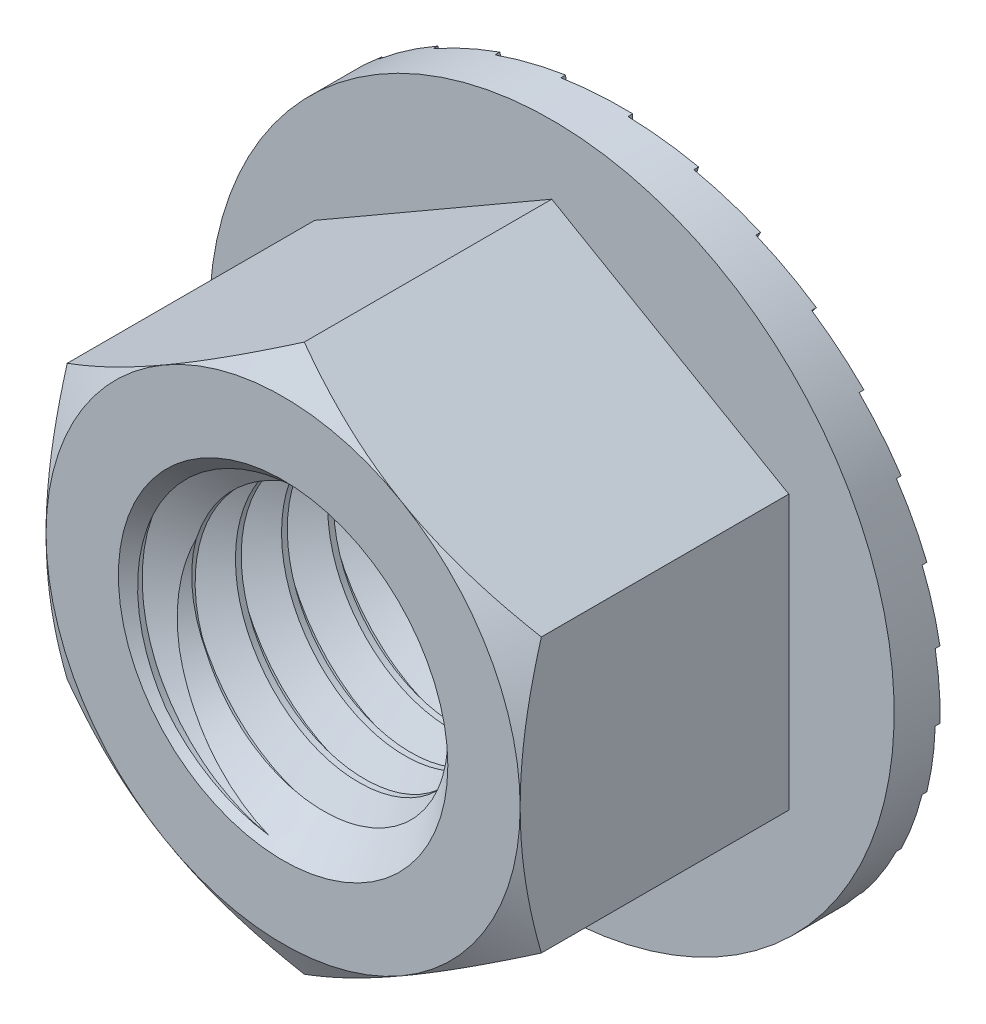
SolidWorks part; units mm, degrees
ref_plane "Front Plane" through (0, 0, 0) normal (0, 0, 1) x (1, 0, 0)
ref_plane "Top Plane" through (0, 0, 0) normal (0, 1, 0) x (1, 0, 0)
ref_plane "Right Plane" through (0, 0, 0) normal (1, 0, 0) x (0, 0, -1)
sketch "Sketch1" plane through (0, 0, 0) normal (0, 0, 1) x (1, 0, 0)
  line L1 (0, 10.3923) -> (-9, 5.1962)
  line L2 (-9, 5.1962) -> (-9, -5.1962)
  line L3 (-9, -5.1962) -> (0, -10.3923)
  line L4 (0, -10.3923) -> (9, -5.1962)
  line L5 (9, -5.1962) -> (9, 5.1962)
  line L6 (9, 5.1962) -> (0, 10.3923)
  circle A0 centre (0, 0) radius 9 construction
  dimension "Hex" = 18
extrude "Extrude1" add sketch "Sketch1" against normal blind 12
sketch "Sketch13" plane through (0, 0, -12) normal (0, 0, -1) x (-1, 0, 0)
  circle A0 centre (0, 0) radius 13
  dimension "Flange od" = 26
extrude "Extrude3" add sketch "Sketch13" against normal blind 1.8
sketch "Sketch2" plane through (0, 0, 0) normal (0, 0, 1) x (1, 0, 0)
  circle A0 centre (0, 0) radius 9 construction
  circle A1 centre (0, 0) radius 9
extrude "Cut-Extrude1" cut sketch "Sketch2" against normal through all draft 60 flip side to cut
sketch "Sketch4" plane through (0, 0, 0) normal (0, 0, 1) x (1, 0, 0)
  circle A0 centre (0, 0) radius 6
  dimension "Thread Dia" = 12
extrude "Cut-Extrude3" cut sketch "Sketch4" against normal through all
sketch "Sketch7" plane through (0, 0, 0) normal (0, 0, 1) x (1, 0, 0)
  circle A4 centre (0, 0) radius 6.254
  circle A5 centre (0, 0) radius 6.254
  dimension "D1" = 0.254
sketch "Sketch8" plane through (0, 0, -12) normal (0, 0, -1) x (-1, 0, 0)
  circle A1 centre (0, 0) radius 6.254
  circle A2 centre (0, 0) radius 6.254 construction
sketch "Sketch5" plane through (0, 0, 0) normal (0, 0, 1) x (1, 0, 0)
  circle A0 centre (0, 0) radius 6 construction
  circle A1 centre (0, 0) radius 6
curve "Helix/Spiral1" pitch 1.75 height 13.75 turns 7.8571 parameters "pitch"=1.75
sketch "Sketch9" plane through (0, 0, 0) normal (1, 0, 0) x (0, 0, -1)
  line L0 (-0.875, 6) -> (-0.6563, 6)
  line L1 (-0.6563, 6) -> (0, 4.8633)
  line L2 (-0.875, 6) -> (-1.5313, 4.8633)
  line L3 (-1.5313, 4.8633) -> (0, 4.8633)
  line L4 (-0.7656, 6) -> (-0.7656, 4.8633) construction
  line L5 (-1.2031, 5.4317) -> (-0.3281, 5.4317) construction
  line L7 (0, 4.8633) -> (0, 6) construction
  line L8 (0, 6) -> (0, -6) construction
  dimension "D1" = 0.2188
  dimension "D2" = 0.875
  dimension "D3" = 60
sketch "Sketch12" plane through (0, 0, 0) normal (0, 0, 1) x (1, 0, 0)
  circle A0 centre (0, 0) radius 4.8633
  circle A1 centre (0, 0) radius 6 construction
  circle A2 centre (0, 0) radius 6
extrude "Extrude2" add sketch "Sketch12" against normal up to surface (12 mm away)
sweep "Cut-Sweep1" cut profiles "Sketch9" path "Helix/Spiral1"
extrude "Cut-Extrude6" cut sketch "Sketch7" against normal through all draft 45
extrude "Cut-Extrude7" cut sketch "Sketch8" against normal through all draft 45
sketch "Sketch14" plane through (0, 0, -12) normal (0, 0, -1) x (-1, 0, 0)
  circle A4 centre (0, 0) radius 8.286
  circle A5 centre (0, 0) radius 8.286
  dimension "D1" = 2.032
extrude "Cut-Extrude8" cut sketch "Sketch14" against normal blind 0.18 flip side to cut
sketch "Sketch15" plane through (0, 0, -11.82) normal (0, 0, -1) x (-1, 0, 0)
  line L0 (-0.8122, 8.2461) -> (-1.2742, 12.9374)
  line L1 (0.8122, 8.2461) -> (1.2742, 12.9374)
  line L2 (0, 0) -> (0.8122, 8.2461) construction
  line L3 (0, 0) -> (-0.8122, 8.2461) construction
  circle A0 centre (0, 0) radius 13 construction
  circle A1 centre (0, 0) radius 8.286 construction
  arc A2 (1.2742, 12.9374) -> (-1.2742, 12.9374) centre (0, 0) ccw
  arc A3 (0.8122, 8.2461) -> (-0.8122, 8.2461) centre (0, 0) ccw
  dimension "D1" = 11.25
extrude "Extrude4" add sketch "Sketch15" along normal up to surface (0.18 mm away) separate body up to face at (-6.254, 0, -12)
sketch "Sketch16" plane through (0, 0, 0) normal (0, 1, 0) x (1, 0, 0)
  line L0 (-1.2742, 11.82) -> (1.2742, 12)
  line L4 (-1.2742, 11.82) -> (1.2742, 11.82)
  line L5 (1.2742, 11.82) -> (1.2742, 12)
  line L6 (1.2742, 12) -> (-1.2742, 12)
  line L7 (-1.2742, 12) -> (-1.2742, 11.82)
  line L8 (-1.2742, 11.82) -> (1.2742, 11.82) construction
  line L9 (1.2742, 11.82) -> (1.2742, 12) construction
  line L10 (1.2742, 12) -> (-1.2742, 12)
  line L11 (-1.2742, 12) -> (-1.2742, 11.82)
  dimension "D1" = 0
extrude "Cut-Extrude9" cut sketch "Sketch16" along normal through all
pattern_circular "CirPattern1" count 32 over 360 about axis through (0, 0, 0) along (0, 0, 1) of bodies 119
combine bodies "Combine1" operation type add bodies to combine 117 119 120 121 122 123 124 125 126 127 128 129 130 131 132 133 134 135 136 137 139 140 141 142 143 144 145 146 147 148 149 150 151
sketch "Sketch17" plane through (0, 0, 0) normal (1, 0, 0) x (0, 0, -1)
  line L0 (12, 13) -> (12, -13) construction
  line L1 (10.2, 13) -> (10.2, -13) construction
  dimension "D1" = 1.8
sketch "Sketch18" plane through (0, 0, -10.2) normal (0, 0, 1) x (1, 0, 0)
  line L0 (0, 0) -> (0, -4.8633) construction
  line L1 (-9, 5.1962) -> (9, 5.1962) construction
  circle A0 centre (0, 0) radius 13
  circle A1 centre (0, 0) radius 13 construction
  circle A2 centre (0, 0) radius 4.8633 construction
equation "\"D2@Sketch9\" = \"pitch@Helix/Spiral1\"*.5"
equation "\"D3@Helix/Spiral1\" = \"pitch@Helix/Spiral1\"+\"Height@Extrude1\""
equation "\"D1@Sketch9\" = \"pitch@Helix/Spiral1\"*.125"
equation "\"D1@Cut-Extrude8\" = \"flange thickness@Extrude3\"*.1"
equation "\"D1@Sketch17\" = \"flange thickness@Extrude3\""
